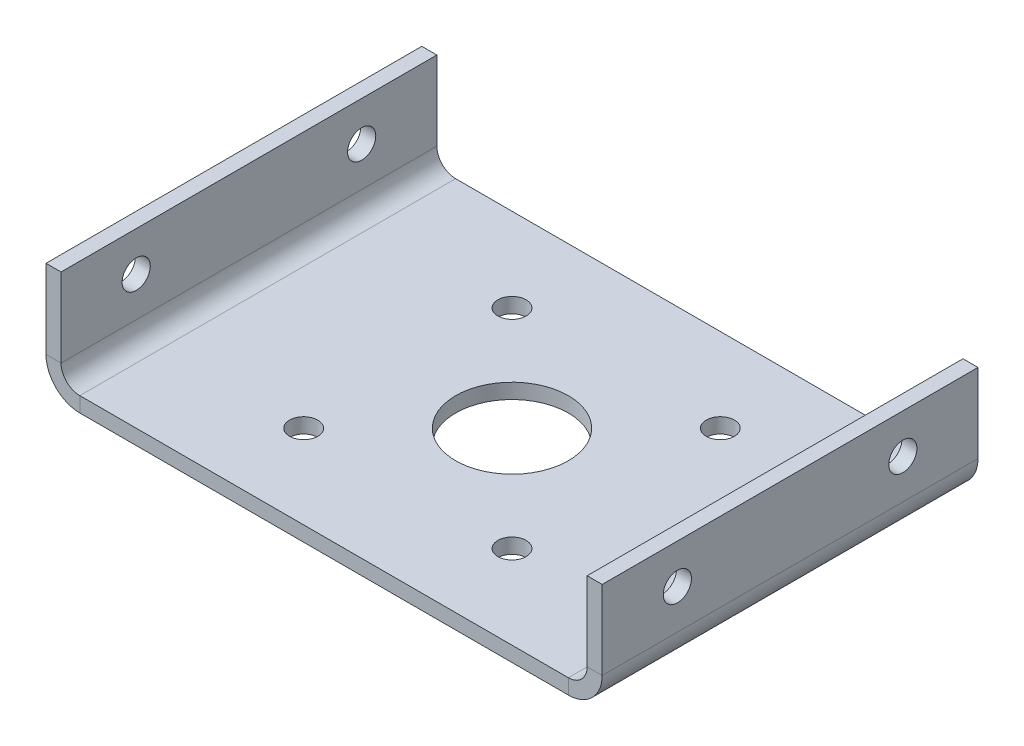
SolidWorks part; units mm, degrees
note: The reader was unsure of these and kept them because the rebuilt part matched: flange length of "Edge-Flange1".
material "Plain Carbon Steel"
ref_plane "Front Plane" through (0, 0, 0) normal (0, 0, 1) x (1, 0, 0)
ref_plane "Top Plane" through (0, 0, 0) normal (0, 1, 0) x (1, 0, 0)
ref_plane "Right Plane" through (0, 0, 0) normal (1, 0, 0) x (0, 0, -1)
sketch "Sketch1" plane through (0, 0, 0) normal (0, 1, 0) x (1, 0, 0)
  line L1 (-148, -100) -> (148, -100)
  line L2 (-148, -100) -> (-148, 100)
  line L3 (-148, 100) -> (148, 100)
  line L4 (148, -100) -> (148, 100)
  line L5 (-148, -100) -> (148, 100) construction
  line L6 (-148, 100) -> (148, -100) construction
  point P0 (0, 0)
  dimension "D1" = 296
  dimension "D2" = 200
base flange "Base-Flange1" sketch "Sketch1" thickness 8 reverse thickness direction no parameters "D1"=3
edge flange "Edge-Flange1" sketch "Sketch10" flange profiles "Sketch10", "Sketch11" flange angle 90 flange length 60 flange position material inside bend radius 10 thickness 8 relief rectangular parameters "D6"=10, "D8"=1
sketch "Sketch10" plane through (-148, 0, 0) normal (-1, 0, 0) x (0, 0, 1)
  line L0 (-100, 0) -> (100, 0) construction
  line L1 (-100, 0) -> (100, 0)
  line L2 (-100, 0) -> (-100, 52)
  line L3 (-100, 52) -> (100, 52)
  line L4 (100, 52) -> (100, 0)
sketch "Sketch11" plane through (148, 0, 0) normal (1, 0, 0) x (0, 0, -1)
  line L0 (-100, 0) -> (100, 0) construction
  line L1 (-100, 0) -> (100, 0)
  line L2 (-100, 0) -> (-100, 52)
  line L3 (-100, 52) -> (100, 52)
  line L4 (100, 52) -> (100, 0)
bend "EdgeBend1" bend radius 10 bend angle 90 parameters "D5"=1
bend "EdgeBend2" bend radius 10 bend angle 90 parameters "D5"=2
sketch "Sketch12" plane through (0, -8, 0) normal (0, -1, 0) x (-1, 0, 0)
  circle A0 centre (0, 0) radius 30
  dimension "D1" = 60
extrude "Cut-Extrude1" cut sketch "Sketch12" against normal blind 10
sketch "Sketch13" plane through (0, -8, 0) normal (0, -1, 0) x (-1, 0, 0)
  line L3 (-55.4372, -55.4372) -> (55.4372, -55.4372) construction
  line L4 (-55.4372, -55.4372) -> (-55.4372, 55.4372) construction
  line L5 (-55.4372, 55.4372) -> (55.4372, 55.4372) construction
  line L6 (55.4372, -55.4372) -> (55.4372, 55.4372) construction
  line L7 (-55.4372, -55.4372) -> (55.4372, 55.4372) construction
  line L8 (-55.4372, 55.4372) -> (55.4372, -55.4372) construction
  circle A0 centre (55.4372, -55.4372) radius 7.5
  point P4 (0, 0)
  dimension "D1" = 15
  dimension "D3" = 78.4
extrude "Cut-Extrude2" cut sketch "Sketch13" against normal blind 10
mirror "Mirror4" about plane through (0, 0, 0) normal (1, 0, 0) of "Cut-Extrude2"
sketch "Sketch15" plane through (-148, 0, 0) normal (-1, 0, 0) x (0, 0, 1)
  line L2 (-100, 0) -> (-100, 52) construction
  line L3 (100, 10) -> (-100, 10) construction
  circle A0 centre (-60, 31) radius 7.5
  dimension "D1" = 15
  dimension "D2" = 40
  dimension "D3" = 21
extrude "Cut-Extrude3" cut sketch "Sketch15" against normal through all
mirror "Mirror5" about plane through (0, 0, 0) normal (0, 0, 1) of "Cut-Extrude3", "Mirror4", "Cut-Extrude2"
sketch "Bend-Lines1" [suppressed] plane through (0, 0, 0) normal (0, 1, 0) x (1, 0, 0)
sketch "Bounding-Box1" [suppressed] plane through (0, 0, 0) normal (0, 1, 0) x (1, 0, 0)
sheet metal parameters "Sheet-Metal1" thickness 8 parameters "D1"=3
flat pattern "Flat-Pattern1" [suppressed]
sketch "Bend-Lines2" plane through (0, 0, 0) normal (0, 1, 0) x (1, 0, 0)
sketch3d "Bounding-Box2" [suppressed]
  line L0 (-100, -100, 0) -> (-100, 100, 0) construction
  line L1 (100, -100, 0) -> (100, 100, 0) construction
  line L2 (-100, -100, 0) -> (100, -100, 0) construction
  line L3 (-100, 100, 0) -> (100, 100, 0) construction
sheet metal parameters "Sheet-Metal2" thickness 8 parameters "D1"=3
flat pattern "Flat-Pattern1"
sketch "Bend-Lines2" plane through (0, 0, 0) normal (0, 1, 0) x (1, 0, 0)
  line L0 (142.9956, -100) -> (142.9956, 100) construction
  line L1 (-142.9956, 100) -> (-142.9956, -100) construction
  line L2 (142.9956, -100) -> (142.9956, 100) construction
  line L3 (-142.9956, 100) -> (-142.9956, -100) construction
sketch3d "Bounding-Box2" [suppressed]
  line L0 (205.9911, 100, 0) -> (-205.9911, 100, 0) construction
  line L1 (205.9911, -100, 0) -> (-205.9911, -100, 0) construction
  line L2 (205.9911, 100, 0) -> (205.9911, -100, 0) construction
  line L3 (-205.9911, 100, 0) -> (-205.9911, -100, 0) construction
bend of the flat pattern "Flatten-<EdgeBend1>1"
bend of the flat pattern "Flatten-<EdgeBend2>1"
sheet metal parameters "Sheet-Metal3" thickness 8 parameters "D1"=3
flat pattern "Flat-Pattern1"
sketch "Bend-Lines2" plane through (0, 0, 0) normal (0, 1, 0) x (1, 0, 0)
  line L0 (142.9956, -100) -> (142.9956, 100) construction
  line L1 (-142.9956, 100) -> (-142.9956, -100) construction
  line L2 (142.9956, -100) -> (142.9956, 100) construction
  line L3 (-142.9956, 100) -> (-142.9956, -100) construction
sketch3d "Bounding-Box2" [suppressed]
  line L0 (205.9911, 100, 0) -> (-205.9911, 100, 0) construction
  line L1 (205.9911, -100, 0) -> (-205.9911, -100, 0) construction
  line L2 (205.9911, 100, 0) -> (205.9911, -100, 0) construction
  line L3 (-205.9911, 100, 0) -> (-205.9911, -100, 0) construction
bend of the flat pattern "Flatten-<EdgeBend1>1"
bend of the flat pattern "Flatten-<EdgeBend2>1"
sheet metal parameters "Sheet-Metal5" thickness 8 parameters "D1"=3
flat pattern "Flat-Pattern1"
sketch "Bend-Lines2" plane through (0, 0, 0) normal (0, 1, 0) x (1, 0, 0)
  line L0 (142.9956, -100) -> (142.9956, 100) construction
  line L1 (-142.9956, 100) -> (-142.9956, -100) construction
  line L2 (142.9956, -100) -> (142.9956, 100) construction
  line L3 (-142.9956, 100) -> (-142.9956, -100) construction
sketch3d "Bounding-Box2" [suppressed]
  line L0 (205.9911, 100, 0) -> (-205.9911, 100, 0) construction
  line L1 (205.9911, -100, 0) -> (-205.9911, -100, 0) construction
  line L2 (205.9911, 100, 0) -> (205.9911, -100, 0) construction
  line L3 (-205.9911, 100, 0) -> (-205.9911, -100, 0) construction
bend of the flat pattern "Flatten-<EdgeBend1>1"
bend of the flat pattern "Flatten-<EdgeBend2>1"
sheet metal parameters "Sheet-Metal7" thickness 8 parameters "D1"=3
flat pattern "Flat-Pattern1"
sketch "Bend-Lines2" plane through (0, 0, 0) normal (0, 1, 0) x (1, 0, 0)
  line L0 (140.9956, -100) -> (140.9956, 100) construction
  line L1 (-140.9956, 100) -> (-140.9956, -100) construction
  line L2 (140.9956, -100) -> (140.9956, 100) construction
  line L3 (-140.9956, 100) -> (-140.9956, -100) construction
sketch3d "Bounding-Box2" [suppressed]
  line L0 (203.9911, 100, 0) -> (-203.9911, 100, 0) construction
  line L1 (203.9911, -100, 0) -> (-203.9911, -100, 0) construction
  line L2 (203.9911, 100, 0) -> (203.9911, -100, 0) construction
  line L3 (-203.9911, 100, 0) -> (-203.9911, -100, 0) construction
bend of the flat pattern "Flatten-<EdgeBend1>1"
bend of the flat pattern "Flatten-<EdgeBend2>1"
sheet metal parameters "Sheet-Metal8" thickness 8 parameters "D1"=3
flat pattern "Flat-Pattern1"
sketch "Bend-Lines2" plane through (0, 0, 0) normal (0, 1, 0) x (1, 0, 0)
  line L0 (140.9956, -100) -> (140.9956, 100) construction
  line L1 (-140.9956, 100) -> (-140.9956, -100) construction
  line L2 (140.9956, -100) -> (140.9956, 100) construction
  line L3 (-140.9956, 100) -> (-140.9956, -100) construction
sketch3d "Bounding-Box2" [suppressed]
  line L0 (193.9911, 100, 0) -> (-193.9911, 100, 0) construction
  line L1 (193.9911, -100, 0) -> (-193.9911, -100, 0) construction
  line L2 (193.9911, 100, 0) -> (193.9911, -100, 0) construction
  line L3 (-193.9911, 100, 0) -> (-193.9911, -100, 0) construction
bend of the flat pattern "Flatten-<EdgeBend1>1"
bend of the flat pattern "Flatten-<EdgeBend2>1"
sheet metal parameters "Sheet-Metal9" thickness 8 parameters "D1"=3
flat pattern "Flat-Pattern1"
sketch "Bend-Lines2" plane through (0, 0, 0) normal (0, 1, 0) x (1, 0, 0)
  line L0 (140.9956, -100) -> (140.9956, 100) construction
  line L1 (-140.9956, 100) -> (-140.9956, -100) construction
  line L2 (140.9956, -100) -> (140.9956, 100) construction
  line L3 (-140.9956, 100) -> (-140.9956, -100) construction
sketch3d "Bounding-Box2" [suppressed]
  line L0 (203.9911, 100, 0) -> (-203.9911, 100, 0) construction
  line L1 (203.9911, -100, 0) -> (-203.9911, -100, 0) construction
  line L2 (203.9911, 100, 0) -> (203.9911, -100, 0) construction
  line L3 (-203.9911, 100, 0) -> (-203.9911, -100, 0) construction
bend of the flat pattern "Flatten-<EdgeBend1>1"
bend of the flat pattern "Flatten-<EdgeBend2>1"
